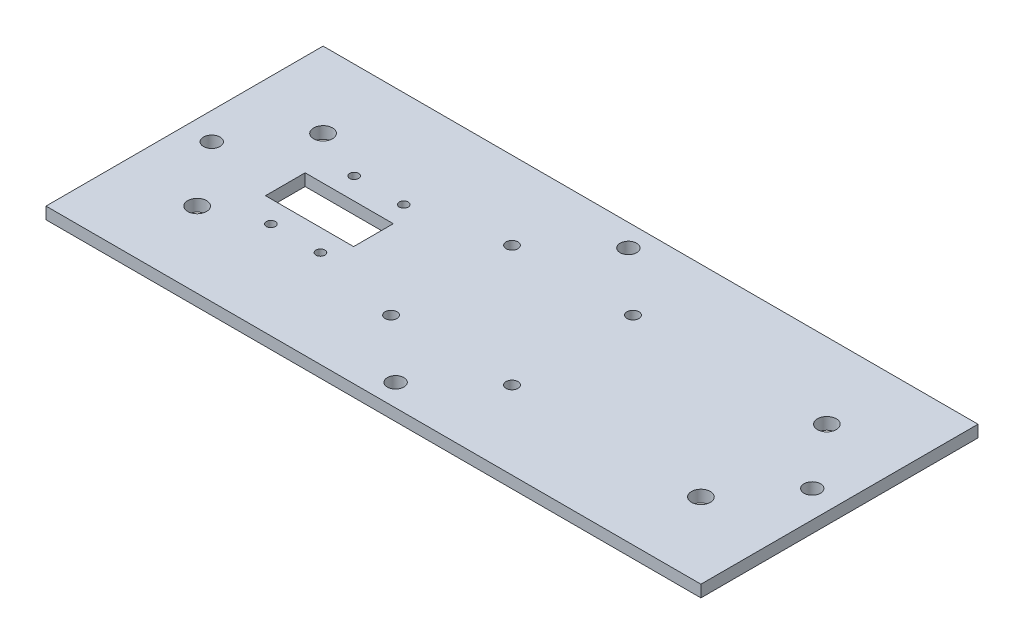
SolidWorks part; units mm, degrees
material "Thornel VCB-20 Carbon Cloth"
ref_plane "Front Plane" through (0, 0, 0) normal (0, 0, 1) x (1, 0, 0)
ref_plane "Top Plane" through (0, 0, 0) normal (0, 1, 0) x (1, 0, 0)
ref_plane "Right Plane" through (0, 0, 0) normal (1, 0, 0) x (0, 0, -1)
sketch "Sketch1" plane through (0, 0, 0) normal (0, 1, 0) x (1, 0, 0)
  line L0 (82.55, -34.925) -> (82.55, 34.925)
  line L1 (82.55, -34.925) -> (-82.55, -34.925)
  line L2 (82.55, 34.925) -> (-82.55, 34.925)
  line L3 (-82.55, -34.925) -> (-82.55, 34.925)
  line L4 (82.55, -34.925) -> (-82.55, 34.925) construction
  line L5 (82.55, 34.925) -> (-82.55, -34.925) construction
  point P1 (0, 0)
  dimension "D1" = 165.1
  dimension "D2" = 69.85
extrude "Boss-Extrude1" add sketch "Sketch1" along normal blind 3
sketch "Sketch6" plane through (0, 0, 0) normal (0, -1, 0) x (1, 0, 0)
  line L0 (-82.55, -34.925) -> (-82.55, 34.925) construction
  line L1 (-57.15, 5) -> (-34.925, 5)
  line L2 (-57.15, 5) -> (-57.15, -5)
  line L3 (-57.15, -5) -> (-34.925, -5)
  line L4 (-34.925, 5) -> (-34.925, -5)
  circle A0 centre (-15.25, 15.25) radius 1.5
  circle A1 centre (15.25, 15.25) radius 1.5
  circle A2 centre (-15.25, -15.25) radius 1.5
  circle A3 centre (15.25, -15.25) radius 1.5
  point P8 (-34.925, 0)
  dimension "D5" = 3
  dimension "D6" = 3
  dimension "D7" = 3
  dimension "D8" = 3
  dimension "D1" = 22.225
  dimension "D2" = 10
  dimension "D3" = 25.4
  dimension "D9" = 15.25
  dimension "D10" = 15.25
  dimension "D11" = 15.25
  dimension "D12" = 15.25
  dimension "D13" = 15.25
  dimension "D14" = 15.25
  dimension "D15" = 15.25
  dimension "D16" = 15.25
extrude "Cut-Extrude1" cut sketch "Sketch6" against normal up to next
sketch "Sketch7" plane through (0, 3, 0) normal (0, 1, 0) x (1, 0, 0)
  line L0 (-82.55, 34.925) -> (-82.55, -34.925) construction
  line L1 (82.55, -34.925) -> (82.55, 34.925) construction
  line L2 (-82.55, -34.925) -> (82.55, -34.925) construction
  line L3 (82.55, 34.925) -> (-82.55, 34.925) construction
  circle A0 centre (-77.47, 29.845) radius 1.5
  circle A1 centre (-77.47, -29.845) radius 1.5
  circle A2 centre (77.47, -29.845) radius 1.5
  circle A3 centre (77.47, 29.845) radius 1.5
  dimension "D9" = 3
  dimension "D10" = 3
  dimension "D11" = 3
  dimension "D12" = 3
  dimension "D1" = 5.08
  dimension "D2" = 5.08
  dimension "D3" = 5.08
  dimension "D4" = 5.08
  dimension "D5" = 5.08
  dimension "D6" = 5.08
  dimension "D7" = 5.08
  dimension "D8" = 5.08
sketch "Sketch8" plane through (0, 3, 0) normal (0, 1, 0) x (1, 0, 0)
  line L0 (-82.55, -34.925) -> (82.55, -34.925) construction
  line L1 (-82.55, 34.925) -> (-82.55, -34.925) construction
  line L2 (82.55, -34.925) -> (82.55, 34.925) construction
  line L3 (82.55, 34.925) -> (-82.55, 34.925) construction
  circle A0 centre (-63.5, -15.875) radius 2.3813
  circle A1 centre (-63.5, 15.875) radius 2.3813
  circle A2 centre (63.5, 15.875) radius 2.3813
  circle A3 centre (63.5, -15.875) radius 2.3813
  dimension "D1" = 4.7625
  dimension "D4" = 4.7625
  dimension "D5" = 4.7625
  dimension "D6" = 4.7625
  dimension "D2" = 19.05
  dimension "D3" = 19.05
  dimension "D7" = 19.05
  dimension "D8" = 19.05
  dimension "D9" = 19.05
  dimension "D10" = 19.05
  dimension "D11" = 19.05
  dimension "D12" = 19.05
extrude "Cut-Extrude3" cut sketch "Sketch8" against normal up to next
sketch "Sketch9" plane through (0, 3, 0) normal (0, 1, 0) x (1, 0, 0)
  line L0 (-82.55, 34.925) -> (-82.55, -34.925) construction
  line L1 (82.55, -34.925) -> (82.55, 34.925) construction
  circle A0 centre (-75.692, 0) radius 2.0828
  circle A1 centre (75.692, 0) radius 2.0828
  dimension "D1" = 6.858
  dimension "D2" = 6.858
extrude "Cut-Extrude5" cut sketch "Sketch9" against normal blind 5.08
sketch "Sketch10" plane through (0, 3, 0) normal (0, 1, 0) x (1, 0, 0)
  line L0 (-82.55, -34.925) -> (82.55, -34.925) construction
  line L1 (82.55, 34.925) -> (-82.55, 34.925) construction
  circle A0 centre (0, -29.337) radius 2.0828
  circle A1 centre (0, 29.337) radius 2.0828
  dimension "D1" = 5.588
  dimension "D2" = 5.588
extrude "Cut-Extrude6" cut sketch "Sketch10" against normal blind 5.08 contours A1 | A0
sketch "Sketch11" plane through (0, 3, 0) normal (0, 1, 0) x (1, 0, 0)
  line L1 (-37.7875, 10.5) -> (-50.2875, 10.5) construction
  line L2 (-37.7875, 10.5) -> (-37.7875, -10.5) construction
  line L3 (-37.7875, -10.5) -> (-50.2875, -10.5) construction
  line L4 (-50.2875, 10.5) -> (-50.2875, -10.5) construction
  line L5 (-37.7875, 10.5) -> (-50.2875, -10.5) construction
  line L6 (-37.7875, -10.5) -> (-50.2875, 10.5) construction
  line L7 (-34.925, 5) -> (-57.15, 5) construction
  circle A0 centre (-50.2875, 10.5) radius 1.125
  circle A1 centre (-37.7875, 10.5) radius 1.125
  circle A2 centre (-37.7875, -10.5) radius 1.125
  circle A3 centre (-50.2875, -10.5) radius 1.125
  point P0 (-44.0375, 0)
  point P9 (-46.0375, 5)
  dimension "D4" = 2.25
  dimension "D5" = 2.25
  dimension "D6" = 2.25
  dimension "D7" = 2.25
  dimension "D1" = 12.5
  dimension "D2" = 21
  dimension "D3" = 2
extrude "Cut-Extrude7" cut sketch "Sketch11" against normal blind 41.91
